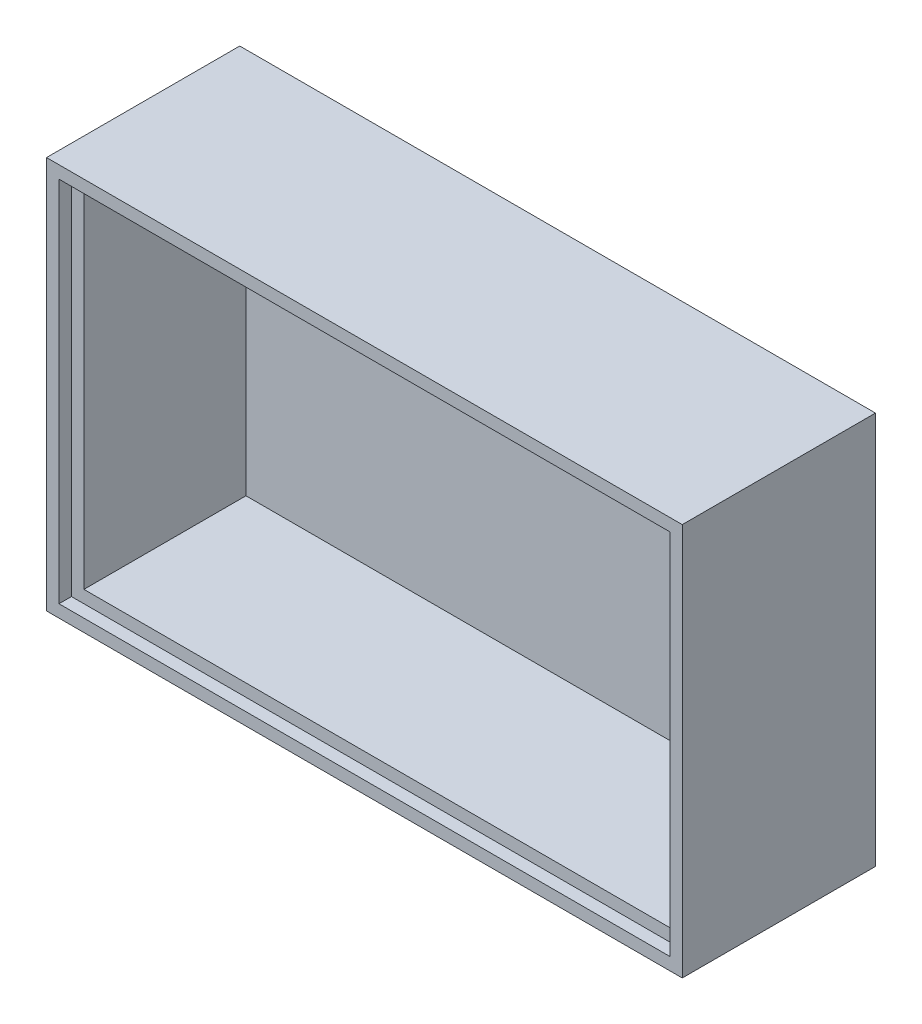
SolidWorks part; units mm, degrees
ref_plane "Přední rovina" through (0, 0, 0) normal (0, 0, 1) x (1, 0, 0)
ref_plane "Horní rovina" through (0, 0, 0) normal (0, 1, 0) x (1, 0, 0)
ref_plane "Pravá rovina" through (0, 0, 0) normal (1, 0, 0) x (0, 0, -1)
sketch "Skica1" plane through (0, 0, 0) normal (0, 0, 1) x (1, 0, 0)
  line L1 (0, 0) -> (98, 0)
  line L2 (0, 0) -> (0, 59)
  line L3 (0, 59) -> (98, 59)
  line L4 (98, 0) -> (98, 59)
  line L5 (-2, 61) -> (100, 61)
  line L6 (-2, 61) -> (-2, -2)
  line L7 (-2, -2) -> (100, -2)
  line L8 (100, 61) -> (100, -2)
  line L9 (2, 57) -> (96, 57)
  line L10 (2, 57) -> (2, 2)
  line L11 (2, 2) -> (96, 2)
  line L12 (96, 57) -> (96, 2)
  dimension "D1" = 102
  dimension "D2" = 63
  dimension "D3" = 2
  dimension "D4" = 2
  dimension "D5" = 2
  dimension "D6" = 2
  dimension "D7" = 2
  dimension "D8" = 2
  dimension "D9" = 2
  dimension "D10" = 2
  dimension "D11" = 55
  dimension "D12" = 94
extrude "Přidat vysunutím1" add sketch "Skica1" along normal blind 3 contours L6 L7 L8 L5
extrude "Přidat vysunutím2" add sketch "Skica1<4>" along normal blind 31 contours L8 L5 L6 L7 L4 L1 L2 L3 region at (49, 59.8011, 0)
sketch "Skica1<4>" plane through (0, 0, 0) normal (0, 0, 1) x (1, 0, 0) same geometry as "Skica1"
extrude "Přidat vysunutím3" add sketch "Skica1<5>" along normal blind 29 contours L1 L4 L3 L2 L9 L12 L11 L10 region at (1.1439, 29.5, 0)
sketch "Skica1<5>" plane through (0, 0, 0) normal (0, 0, 1) x (1, 0, 0) same geometry as "Skica1"
